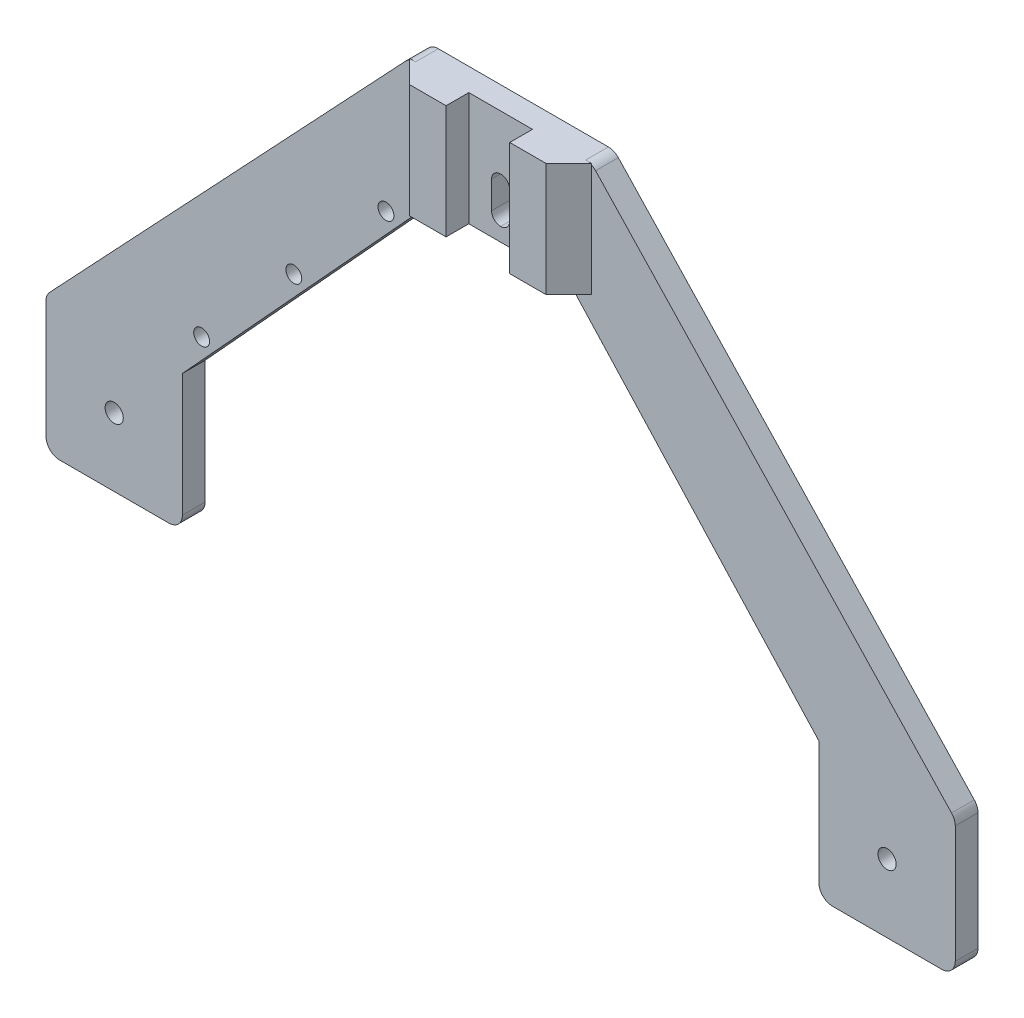
SolidWorks part; units mm, degrees
ref_plane "Płaszczyzna przednia" through (0, 0, 0) normal (0, 0, 1) x (1, 0, 0)
ref_plane "Płaszczyzna górna" through (0, 0, 0) normal (0, 1, 0) x (1, 0, 0)
ref_plane "Płaszczyzna prawa" through (0, 0, 0) normal (1, 0, 0) x (0, 0, -1)
sketch "Szkic2" plane through (0, 0, 0) normal (0, 0, 1) x (1, 0, 0)
  line L0 (0, 0) -> (30, 0)
  line L1 (30, 0) -> (30, 30)
  line L2 (30, 30) -> (85, 90)
  line L3 (85, 90) -> (115, 90)
  line L4 (115, 90) -> (170, 30)
  line L5 (170, 30) -> (170, 0)
  line L6 (170, 0) -> (200, 0)
  line L7 (200, 0) -> (200, 30)
  line L8 (200, 30) -> (120, 115)
  line L9 (120, 115) -> (80, 115)
  line L10 (80, 115) -> (0, 30)
  line L11 (0, 30) -> (0, 0)
  point P11 (0, 0)
  point P14 (0, 0)
  point P15 (0, 0)
  point P16 (0, 0)
  point P17 (0, 0)
  point P18 (0, 0)
  point P19 (0, 0)
  point P20 (0, 0)
  point P21 (0, 0)
  point P22 (0, 0)
  point P23 (0, 0)
  point P24 (0, 0)
  point P25 (0, 0)
  point P26 (0, 0)
  point P27 (0, 0)
  point P28 (0, 0)
  point P29 (0, 0)
  point P30 (0, 0)
  point P31 (0, 0)
  point P32 (0, 0)
  point P33 (0, 0)
  point P34 (0, 0)
  point P35 (0, 0)
  point P36 (0, 0)
  point P37 (0, 0)
  point P38 (0, 0)
  point P39 (0, 0)
  point P40 (0, 0)
  point P41 (0, 0)
  point P42 (0, 0)
  point P43 (0, 0)
  point P44 (0, 0)
  point P45 (0, 0)
  point P46 (0, 0)
extrude "Dodanie-wyciągnięcie1" add sketch "Szkic2" along normal blind 5
sketch "Szkic3" plane through (0, 0, 5) normal (0, 0, 1) x (1, 0, 0)
  circle A0 centre (15, 15) radius 2
  circle A1 centre (185, 15) radius 2
extrude "Wytnij-wyciągnięcie1" cut sketch "Szkic3" against normal blind 5
sketch "Szkic4" plane through (0, 0, 5) normal (0, 0, 1) x (1, 0, 0)
  line L1 (98, 103) -> (102, 103)
  line L2 (98, 103) -> (98, 93)
  line L3 (98, 93) -> (102, 93)
  line L4 (102, 103) -> (102, 93)
  point P4 (0, 0)
  point P5 (0, 0)
  point P6 (0, 0)
  point P7 (0, 0)
  point P8 (0, 0)
  point P9 (0, 0)
  point P10 (0, 0)
  point P11 (0, 0)
  point P12 (0, 0)
  point P13 (0, 0)
extrude "Wytnij-wyciągnięcie2" cut sketch "Szkic4" against normal blind 5
fillet "Zaokrąglenie1" radius 3 8 edges at (0, 30, 2.5) (80, 115, 2.5) (120, 115, 2.5) (200, 30, 2.5) (200, 0, 2.5) (170, 0, 2.5) (0, 0, 2.5) (30, 0, 2.5)
fillet "Zaokrąglenie2" radius 2 4 edges at (98, 103, 2.5) (102, 103, 2.5) (102, 93, 2.5) (98, 93, 2.5)
sketch "Szkic5" plane through (0, 0, 5) normal (0, 0, 1) x (1, 0, 0)
  line L0 (85, 90) -> (115, 90) construction
  line L1 (107, 90) -> (120, 90)
  line L2 (107, 90) -> (107, 115)
  line L3 (107, 115) -> (120, 115)
  line L4 (120, 90) -> (120, 115)
  line L5 (118.7038, 115) -> (81.2962, 115) construction
  line L7 (93, 90) -> (80, 90)
  line L8 (93, 90) -> (93, 115)
  line L9 (93, 115) -> (80, 115)
  line L10 (80, 90) -> (80, 115)
extrude "Dodanie-wyciągnięcie2" add sketch "Szkic5" along normal blind 5
chamfer "Sfazowanie1" distance 5 angle 45 2 edges at (80, 102.5, 10) (120, 102.5, 10)
sketch "Szkic6" plane through (0, 0, 5) normal (0, 0, 1) x (1, 0, 0)
  line L0 (30, 30) -> (85, 90) construction
  circle A0 centre (74.778, 83.2884) radius 1.75
  circle A1 centre (34.2345, 39.0592) radius 1.75
  circle A2 centre (54.5063, 61.1738) radius 1.75
  point P9 (0, 0)
  dimension "D1" = 3
  dimension "D4" = 10
  dimension "D2" = 3
  dimension "D3" = 3
  dimension "D5" = 30
  dimension "D6" = 30
extrude "Wytnij-wyciągnięcie3" cut sketch "Szkic6" against normal up to next
